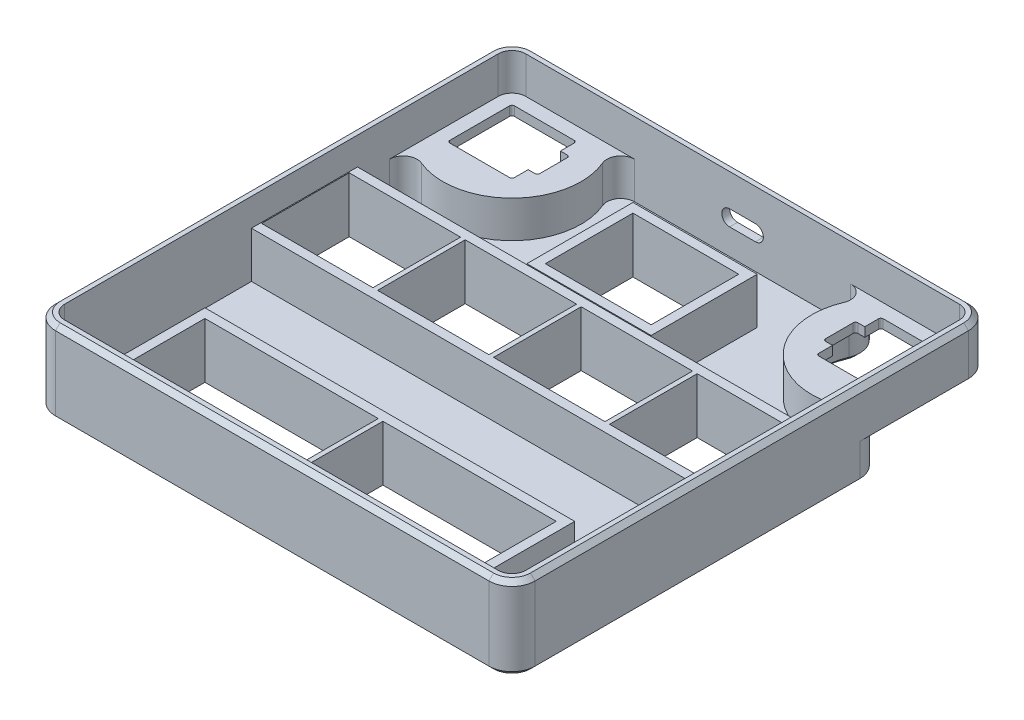
SolidWorks part; units mm, degrees
ref_plane "Front Plane" through (0, 0, 0) normal (0, 0, 1) x (1, 0, 0)
ref_plane "Top Plane" through (0, 0, 0) normal (0, 1, 0) x (1, 0, 0)
ref_plane "Right Plane" through (0, 0, 0) normal (1, 0, 0) x (0, 0, -1)
sketch "草图1" plane through (0, 0, 0) normal (0, 1, 0) x (1, 0, 0)
  line L0 (0, 55) -> (100, 55) construction
  line L1 (3, 0) -> (97, 0)
  line L2 (0, 3) -> (0, 97)
  line L3 (3, 100) -> (97, 100)
  line L4 (100, 3) -> (100, 97)
  line L7 (38.525, 87.7) -> (61.475, 87.7)
  line L8 (38.525, 87.7) -> (38.525, 68.7)
  line L9 (38.525, 68.7) -> (61.475, 68.7)
  line L10 (61.475, 87.7) -> (61.475, 68.7)
  line L11 (38.525, 87.7) -> (61.475, 68.7) construction
  line L12 (38.525, 68.7) -> (61.475, 87.7) construction
  line L13 (50, 0) -> (50, 9.9) construction
  line L14 (11.9, 21.5) -> (49.5, 21.5)
  line L15 (11.9, 21.5) -> (11.9, 2.5)
  line L16 (11.9, 2.5) -> (49.5, 2.5)
  line L17 (49.5, 21.5) -> (49.5, 2.5)
  line L18 (11.9, 21.5) -> (49.5, 2.5) construction
  line L19 (11.9, 2.5) -> (49.5, 21.5) construction
  line L25 (99.8, 64.5) -> (75.65, 64.5)
  line L30 (99.8, 64.5) -> (99.8, 45.5)
  line L31 (99.8, 45.5) -> (75.65, 45.5)
  line L32 (75.65, 64.5) -> (75.65, 45.5)
  line L33 (99.8, 64.5) -> (75.65, 45.5) construction
  line L34 (99.8, 45.5) -> (75.65, 64.5) construction
  line L38 (25.35, 45.5) -> (49.5, 45.5)
  line L39 (74.65, 64.5) -> (50.5, 64.5)
  line L40 (74.65, 64.5) -> (74.65, 45.5)
  line L41 (74.65, 45.5) -> (50.5, 45.5)
  line L42 (50.5, 64.5) -> (50.5, 45.5)
  line L43 (74.65, 64.5) -> (50.5, 45.5) construction
  line L44 (74.65, 45.5) -> (50.5, 64.5) construction
  line L45 (49.5, 64.5) -> (49.5, 45.5)
  line L46 (25.35, 64.5) -> (49.5, 64.5)
  line L47 (25.35, 64.5) -> (25.35, 45.5)
  line L48 (0.2, 45.5) -> (24.35, 45.5)
  line L49 (24.35, 64.5) -> (24.35, 45.5)
  line L50 (0.2, 64.5) -> (24.35, 64.5)
  line L51 (0.2, 64.5) -> (0.2, 45.5)
  line L52 (50, 12) -> (30.7, 12) construction
  line L53 (88.1, 2.5) -> (50.5, 2.5)
  line L54 (50.5, 21.5) -> (50.5, 2.5)
  line L55 (88.1, 21.5) -> (50.5, 21.5)
  line L56 (88.1, 21.5) -> (88.1, 2.5)
  arc A0 (0, 97) -> (3, 100) centre (3, 97) cw
  arc A1 (100, 97) -> (97, 100) centre (97, 97) ccw
  arc A2 (97, 0) -> (100, 3) centre (97, 3) ccw
  arc A3 (3, 0) -> (0, 3) centre (3, 3) cw
  point P6 (0, 100)
  point P12 (100, 0)
  point P15 (0, 0)
  point P16 (50, 78.2)
  point P17 (50, 0)
  point P27 (50, 100)
  point P29 (50, 55)
  point P30 (87.725, 55)
  point P31 (62.575, 55)
  point P43 (30.7, 12)
  dimension "D3" = 3
  dimension "D4" = 3
  dimension "D12" = 12.275
  dimension "D14" = 12
  dimension "D1" = 100
  dimension "D2" = 100
  dimension "D5" = 19
  dimension "D6" = 22.95
  dimension "D7" = 21.8
  dimension "D8" = 19.3
  dimension "D9" = 37.6
  dimension "D10" = 24.15
  dimension "D11" = 45
  dimension "D13" = 25.15
extrude "凸台-拉伸7" add sketch "草图1" along normal blind 2
sketch "草图4" plane through (0, 2, 0) normal (0, 1, 0) x (1, 0, 0)
  line L0 (3, 100) -> (97, 100) construction
  line L2 (0, 97) -> (0, 3) construction
  line L3 (100, 3) -> (100, 97) construction
  circle A0 centre (10, 90) radius 15
  circle A1 centre (90, 90) radius 15
  dimension "D1" = 10
  dimension "D3" = 30
  dimension "D4" = 10
  dimension "D6" = 30
  dimension "D2" = 10
  dimension "D5" = 10
extrude "切除-拉伸1" cut sketch "草图4" against normal blind 18
fillet "圆角1" radius 3 2 edges at (0, 1, -78.8197) (21.1803, 1, -100)
fillet "圆角2" radius 3 2 edges at (100, 1, -78.8197) (78.8197, 1, -100)
extrude "拉伸-薄壁3" add sketch "草图1<6>" along normal blind 12 thin contours L7 L10 L9 L8 thin type one direction wall 2
sketch "草图1<6>" plane through (0, 0, 0) normal (0, 1, 0) x (1, 0, 0) same geometry as "草图1"
extrude "拉伸-薄壁4" add sketch "草图1<7>" along normal blind 12 thin contours L50 L49 L48 L51 | L46 L45 L38 L47 | L39 L42 L41 L40 | L25 L32 L31 L30 thin type one direction wall 2
sketch "草图1<7>" plane through (0, 0, 0) normal (0, 1, 0) x (1, 0, 0) same geometry as "草图1"
extrude "拉伸-薄壁5" add sketch "草图1<8>" along normal blind 12 thin contours L14 L17 L16 L15 | L55 L54 L53 L56 thin type one direction wall 2
sketch "草图1<8>" plane through (0, 0, 0) normal (0, 1, 0) x (1, 0, 0) same geometry as "草图1"
sketch "草图10" plane through (0, 2, 0) normal (0, 1, 0) x (1, 0, 0)
  line L1 (26.5831, 100) -> (73.4169, 100)
  line L3 (3, 0) -> (97, 0) construction
  line L5 (0, 73.4169) -> (0, 3)
  line L6 (3, 0) -> (97, 0)
  line L7 (100, 3) -> (100, 73.4169)
  arc A0 (4.1667, 76.1807) -> (0, 73.4169) centre (3, 73.4169) ccw construction
  arc A1 (4.1667, 76.1807) -> (0, 73.4169) centre (3, 73.4169) ccw
  arc A2 (4.1667, 76.1807) -> (23.8193, 95.8333) centre (10, 90) ccw construction
  arc A3 (26.5831, 100) -> (23.8193, 95.8333) centre (26.5831, 97) ccw construction
  arc A4 (26.5831, 100) -> (23.8193, 95.8333) centre (26.5831, 97) ccw
  arc A5 (4.1667, 76.1807) -> (23.8193, 95.8333) centre (10, 90) ccw
  arc A6 (100, 73.4169) -> (95.8333, 76.1807) centre (97, 73.4169) ccw construction
  arc A7 (76.1807, 95.8333) -> (95.8333, 76.1807) centre (90, 90) ccw construction
  arc A8 (76.1807, 95.8333) -> (73.4169, 100) centre (73.4169, 97) ccw construction
  arc A9 (100, 73.4169) -> (95.8333, 76.1807) centre (97, 73.4169) ccw
  arc A10 (76.1807, 95.8333) -> (95.8333, 76.1807) centre (90, 90) ccw
  arc A11 (76.1807, 95.8333) -> (73.4169, 100) centre (73.4169, 97) ccw
  arc A12 (0, 3) -> (3, 0) centre (3, 3) ccw construction
  arc A13 (97, 0) -> (100, 3) centre (97, 3) ccw construction
  arc A14 (97, 0) -> (100, 3) centre (97, 3) ccw
  arc A15 (0, 3) -> (3, 0) centre (3, 3) ccw
extrude "拉伸-薄壁7" add sketch "草图10" along normal blind 18 from surface thin starting at face at (50, 0, -56.3056) thin type one direction wall 2
sketch "草图11" plane through (0, 18, 0) normal (0, 1, 0) x (1, 0, 0)
  line L1 (26.5831, 102) -> (73.4169, 102) construction
  line L8 (26.5831, 102) -> (73.4169, 102)
  line L11 (73.4169, 102) -> (102, 102)
  line L12 (26.5831, 102) -> (-2, 102)
  line L14 (-2, 73.4169) -> (26.5831, 73.4169)
  line L16 (102, 73.4169) -> (102, 3) construction
  line L19 (-2, 73.4169) -> (-2, 102)
  line L20 (26.5831, 102) -> (26.5831, 73.4169)
  line L21 (73.4169, 102) -> (73.4169, 73.4169)
  line L22 (73.4169, 73.4169) -> (102, 73.4169)
  line L23 (26.5831, 100) -> (73.4169, 100) construction
  line L24 (26.5831, 100) -> (73.4169, 100)
  line L25 (-2, 3) -> (-2, 73.4169) construction
  line L26 (-2, 3) -> (-2, 73.4169) construction
  line L27 (102, 73.4169) -> (102, 3) construction
  line L28 (102, 73.4169) -> (102, 102)
extrude "切除-拉伸8" cut sketch "草图11" against normal blind 10 contours L12 L19 L14 L20 | L11 L28 L22 L21
sketch "草图13" plane through (0, 8, 0) normal (0, 1, 0) x (1, 0, 0)
  line L1 (18.5, 93.5) -> (17, 93.5)
  line L3 (19, 93) -> (19, 87)
  line L6 (26.5831, 102) -> (26.5831, 100) construction
  line L7 (18.5, 86.5) -> (17, 86.5)
  line L8 (19, 93.5) -> (17, 86.5) construction
  line L10 (26.5831, 102) -> (26.5831, 100)
  line L11 (-2, 73.4169) -> (0, 73.4169)
  line L14 (-2, 3) -> (-2, 73.4169) construction
  line L15 (-2, 3) -> (-2, 73.4169) construction
  line L16 (-2, 73.4169) -> (-2, 97)
  line L17 (3, 102) -> (26.5831, 102)
  line L18 (17, 93.5) -> (19, 86.5) construction
  line L19 (3.5, 97) -> (16.5, 97)
  line L20 (3, 96.5) -> (3, 83.5)
  line L21 (3.5, 83) -> (16.5, 83)
  line L22 (17, 96.5) -> (17, 93.5)
  line L23 (3, 97) -> (17, 83) construction
  line L24 (3, 83) -> (17, 97) construction
  line L25 (17, 86.5) -> (17, 83.5)
  arc A0 (19, 87) -> (18.5, 86.5) centre (18.5, 87) cw
  arc A1 (19, 93) -> (18.5, 93.5) centre (18.5, 93) ccw
  arc A2 (16.5, 83) -> (17, 83.5) centre (16.5, 83.5) ccw
  arc A3 (4.1667, 76.1807) -> (0, 73.4169) centre (3, 73.4169) ccw construction
  arc A4 (4.1667, 76.1807) -> (23.8193, 95.8333) centre (10, 90) ccw construction
  arc A5 (26.5831, 100) -> (23.8193, 95.8333) centre (26.5831, 97) ccw construction
  arc A6 (3, 83.5) -> (3.5, 83) centre (3.5, 83.5) ccw
  arc A7 (3.5, 97) -> (3, 96.5) centre (3.5, 96.5) ccw
  arc A8 (16.5, 97) -> (17, 96.5) centre (16.5, 96.5) cw
  arc A13 (4.1667, 76.1807) -> (0, 73.4169) centre (3, 73.4169) ccw
  arc A15 (4.1667, 76.1807) -> (23.8193, 95.8333) centre (10, 90) ccw
  arc A16 (26.5831, 100) -> (23.8193, 95.8333) centre (26.5831, 97) ccw
  arc A17 (-2, 97) -> (3, 102) centre (3, 97) cw
  point P14 (10, 90)
  point P19 (0, 0)
  point P20 (18, 90)
  point P21 (0, 0)
  point P22 (0, 0)
  dimension "D1" = 5
  dimension "D2" = 12
  dimension "D9" = 0.5
  dimension "D10" = 0.5
  dimension "D3" = 12
  dimension "D4" = 14
  dimension "D5" = 14
  dimension "D6" = 2
  dimension "D7" = 7
  dimension "D8" = 7
extrude "凸台-拉伸8" add sketch "草图13" along normal blind 2
sketch "草图15" plane through (0, 8, 0) normal (0, 1, 0) x (1, 0, 0)
  line L0 (73.4169, 102) -> (97, 102)
  line L1 (102, 97) -> (102, 73.4169)
  line L2 (83, 86.5) -> (83, 83.5)
  line L8 (100, 73.4169) -> (102, 73.4169) construction
  line L13 (73.4169, 102) -> (73.4169, 100) construction
  line L14 (100, 73.4169) -> (102, 73.4169)
  line L15 (73.4169, 102) -> (73.4169, 100)
  line L16 (83.5, 97) -> (96.5, 97)
  line L17 (83, 96.5) -> (83, 93.5)
  line L18 (83.5, 83) -> (96.5, 83)
  line L19 (97, 96.5) -> (97, 83.5)
  line L20 (83, 97) -> (97, 83) construction
  line L21 (83, 83) -> (97, 97) construction
  line L22 (83, 93.5) -> (81.5, 93.5)
  line L24 (83, 86.5) -> (81.5, 86.5)
  line L25 (81, 93) -> (81, 87)
  line L26 (83, 93.5) -> (81, 86.5) construction
  line L27 (83, 86.5) -> (81, 93.5) construction
  arc A0 (100, 73.4169) -> (95.8333, 76.1807) centre (97, 73.4169) ccw construction
  arc A1 (100, 73.4169) -> (95.8333, 76.1807) centre (97, 73.4169) ccw
  arc A2 (102, 97) -> (97, 102) centre (97, 97) ccw
  arc A7 (83, 96.5) -> (83.5, 97) centre (83.5, 96.5) cw
  arc A8 (81, 93) -> (81.5, 93.5) centre (81.5, 93) cw
  arc A9 (76.1807, 95.8333) -> (95.8333, 76.1807) centre (90, 90) ccw construction
  arc A10 (76.1807, 95.8333) -> (73.4169, 100) centre (73.4169, 97) ccw construction
  arc A11 (81, 87) -> (81.5, 86.5) centre (81.5, 87) ccw
  arc A12 (76.1807, 95.8333) -> (95.8333, 76.1807) centre (90, 90) ccw
  arc A13 (76.1807, 95.8333) -> (73.4169, 100) centre (73.4169, 97) ccw
  arc A14 (83.5, 83) -> (83, 83.5) centre (83.5, 83.5) cw
  arc A15 (97, 83.5) -> (96.5, 83) centre (96.5, 83.5) cw
  arc A16 (97, 96.5) -> (96.5, 97) centre (96.5, 96.5) ccw
  point P11 (82, 90)
  point P13 (90, 90)
  dimension "D1" = 5
  dimension "D2" = 12
  dimension "D9" = 0.5
  dimension "D3" = 12
  dimension "D4" = 14
  dimension "D5" = 7
  dimension "D6" = 8
  dimension "D7" = 7
  dimension "D8" = 2
extrude "凸台-拉伸9" add sketch "草图15" along normal blind 2
sketch "草图18" plane through (0, 10, 0) normal (0, 1, 0) x (1, 0, 0)
  line L2 (0, 73.4169) -> (-2, 73.4169) construction
  line L3 (26.5831, 102) -> (26.5831, 100) construction
  line L6 (0, 73.4169) -> (-2, 73.4169)
  line L7 (26.5831, 102) -> (26.5831, 100)
  line L8 (-2, 97) -> (-2, 73.4169) construction
  line L9 (26.5831, 102) -> (3, 102) construction
  line L10 (-2, 97) -> (-2, 73.4169)
  line L11 (26.5831, 102) -> (3, 102)
  line L16 (0, 73.4169) -> (0, 97)
  line L17 (3, 100) -> (26.5831, 100)
  line L24 (73.4169, 102) -> (73.4169, 100) construction
  line L25 (73.4169, 102) -> (73.4169, 100)
  line L26 (100, 73.4169) -> (102, 73.4169) construction
  line L27 (100, 73.4169) -> (102, 73.4169)
  line L28 (73.4169, 102) -> (97, 102)
  line L29 (102, 97) -> (102, 73.4169)
  line L30 (73.4169, 100) -> (97, 100)
  line L31 (100, 97) -> (100, 73.4169)
  arc A0 (3, 102) -> (-2, 97) centre (3, 97) ccw construction
  arc A1 (3, 102) -> (-2, 97) centre (3, 97) ccw
  arc A6 (102, 97) -> (97, 102) centre (97, 97) ccw
  arc A7 (97, 100) -> (100, 97) centre (97, 97) cw
  arc A8 (0, 97) -> (3, 100) centre (3, 97) cw
  dimension "D1" = 5
  dimension "D2" = 3
  dimension "D3" = 3
extrude "凸台-拉伸12" add sketch "草图18" along normal blind 8
chamfer "倒角1" distance 1 angle 45 12 edges at (80.8076, 0, -80.8076) (99.7639, 0, -77.5835) (77.5835, 0, -99.7639) (50, 0, -102) (22.4165, 0, -99.7639) (19.1924, 0, -80.8076) (0.2361, 0, -77.5835) (-2, 0, -38.2084) (-0.5355, 0, 0.5355) (50, 0, 2) (102, 0, -38.2084) (100.5355, 0, 0.5355)
chamfer "倒角2" distance 1 angle 45 8 edges at (100.5355, 18, 0.5355) (50, 18, 2) (102, 18, -50) (-0.5355, 18, 0.5355) (50, 18, -102) (-2, 18, -50) (100.5355, 18, -100.5355) (-0.5355, 18, -100.5355)
ref_plane "基准面3" through (0, 0, -102) normal (0, 0, -1) x (-1, 0, 0)
sketch "草图20" plane through (0, 0, -102) normal (0, 0, -1) x (-1, 0, 0)
  line L0 (-3, 17) -> (-97, 17) construction
  line L1 (-3, 17) -> (-97, 17)
  line L2 (-50, 17) -> (-50, 1) construction
  line L3 (-73.4169, 1) -> (-26.5831, 1) construction
  line L4 (-52.8, 9.3) -> (-47.2, 9.3) construction
  line L5 (-52.8, 11) -> (-47.2, 11)
  line L6 (-52.8, 7.6) -> (-47.2, 7.6)
  line L7 (-52.8, 13) -> (-47.2, 13)
  line L8 (-52.8, 5.6) -> (-47.2, 5.6)
  arc A0 (-52.8, 11) -> (-52.8, 7.6) centre (-52.8, 9.3) ccw
  arc A1 (-47.2, 7.6) -> (-47.2, 11) centre (-47.2, 9.3) ccw
  arc A2 (-47.2, 5.6) -> (-47.2, 13) centre (-47.2, 9.3) ccw
  arc A3 (-52.8, 13) -> (-52.8, 5.6) centre (-52.8, 9.3) ccw
  point P8 (-50, 9.3)
  point P14 (-54.5, 9.3)
  point P15 (-45.5, 9.3)
  dimension "D1" = 1.7
  dimension "D2" = 6
  dimension "D3" = 9
  dimension "D4" = 2
extrude "切除-拉伸9" cut sketch "草图20" against normal blind 2 contours L6 A1 L5 A0 region at (50, 9.3, -102)
extrude "切除-拉伸10" cut sketch "草图20<3>" against normal blind 0.3 contours A3 L8 A2 L7
sketch "草图20<3>" plane through (0, 0, -102) normal (0, 0, -1) x (-1, 0, 0) same geometry as "草图20"
chamfer "倒角3" distance 0.32 angle 45 4 edges at (50, 5.6, -102) (43.5, 9.3, -102) (50, 13, -102) (56.5, 9.3, -102)
extrude "切除-拉伸12" cut sketch "草图1<11>" along normal blind 12 contours L25 L32 L31 L30 | L39 L42 L41 L40 | L46 L45 L38 L47 | L50 L49 L48 L51 | L55 L54 L53 L56 | L14 L17 L16 L15
sketch "草图1<11>" plane through (0, 0, 0) normal (0, 1, 0) x (1, 0, 0) same geometry as "草图1"
